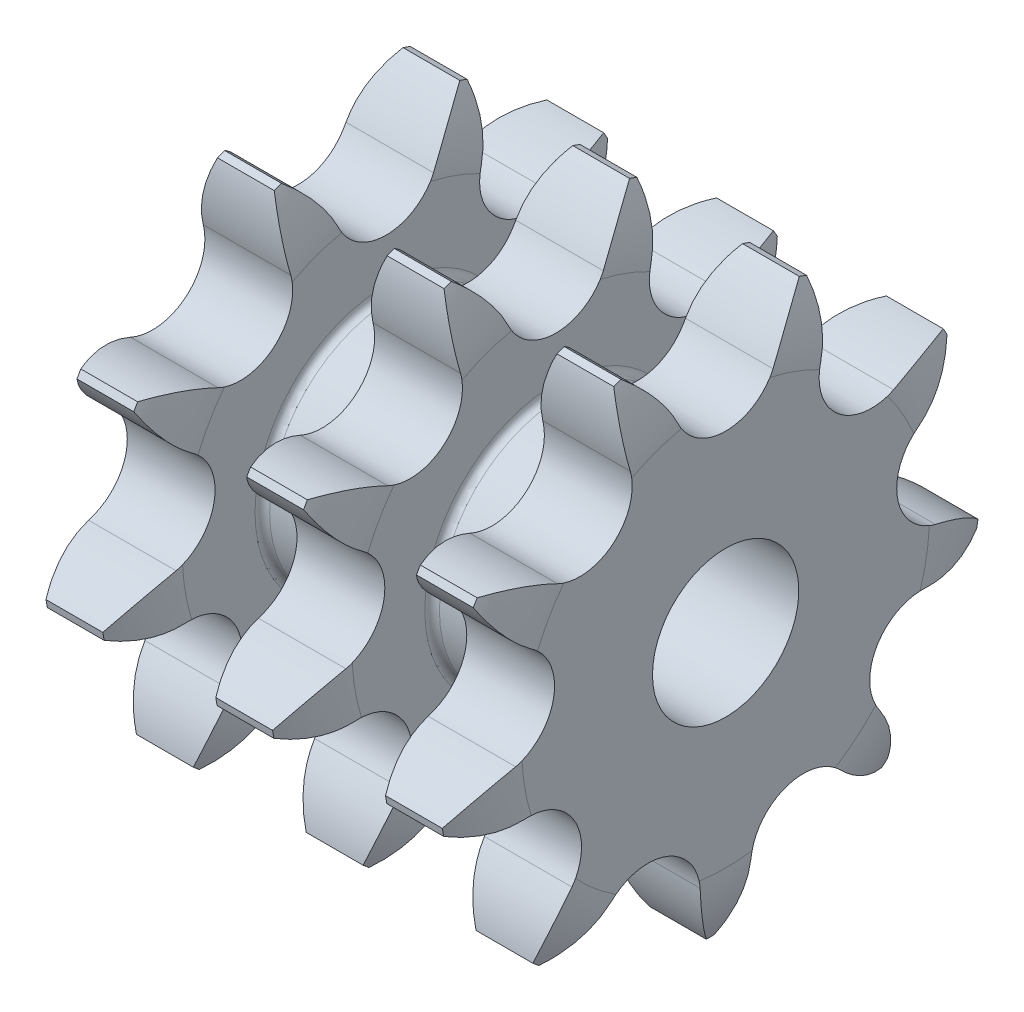
SolidWorks part; units mm, degrees
ref_plane "Plane1" through (0, 0, 0) normal (0, 0, 1) x (1, 0, 0)
ref_plane "Plane2" through (0, 0, 0) normal (0, 1, 0) x (1, 0, 0)
ref_plane "Plane3" through (0, 0, 0) normal (1, 0, 0) x (0, 0, -1)
sketch "Clipboard" plane through (0, 0, 0) normal (0, 1, 0) x (1, 0, 0)
  line L0 (0, 0) -> (12.5436, -1.9867)
  line L1 (-15, 0) -> (100, 0) construction
  line L2 (0, 0) -> (-0.8416, 0.9512)
  line L3 (0, 0) -> (-11.863, 4.5341)
  line L4 (0, 0) -> (3.0618, 0.4849)
  line L5 (0, 0) -> (-2.8109, -1.0484)
  line L6 (0, 0) -> (-29.0469, -19.598)
  line L7 (-0.8416, 0.9512) -> (35.5852, 8.6939)
  line L8 (-76.2, 38.1) -> (-75.2, 38.1)
  line L9 (-73.4259, 41.6592) -> (-72.8306, 41.7344)
  line L10 (-73.4741, 12.7512) -> (-59.5541, 12.7512)
  circle A0 centre (0, 0) radius 4.255
  circle A1 centre (0, 0) radius 10.1515
  circle A2 centre (0, 0) radius 25
  dimension "Num_teeth" = 9
  dimension "Thickness" = 35.04
  dimension "Fillet_rad" = 0.6
sketch "BasProSke" plane through (0, 0, 0) normal (0, 1, 0) x (1, 0, 0)
  line L0 (-10, 0) -> (60, 0) construction
  line L1 (0, 0) -> (0, 16.7129)
  line L2 (0, 0) -> (35.04, 0)
  line L3 (35.04, 0) -> (35.04, 16.7129)
  line L4 (33.77, 22.2487) -> (1.27, 22.2487)
  arc A0 (0, 16.7129) -> (1.27, 22.2487) centre (12.7, 16.7129) cw
  arc A1 (35.04, 16.7129) -> (33.77, 22.2487) centre (22.34, 16.7129) ccw
  dimension "D1" = 12.7
  dimension "Thickness" = 35.04
  dimension "Diameter" = 44.4973
  dimension "G1" = 1.27
revolve "Base-Revolve" add sketch "BasProSke" angle 360 about L0
sketch "GrvSke" plane through (0, 0, 0) normal (0, 1, 0) x (1, 0, 0)
  line L0 (7.2, 16.7129) -> (7.2, 10.7515)
  line L1 (7.8, 10.1515) -> (13.32, 10.1515)
  line L2 (13.92, 10.7515) -> (13.92, 16.7129)
  line L3 (5.93, 22.2487) -> (15.19, 22.2487)
  line L4 (10.56, 0) -> (10.56, 52.07) construction
  line L5 (-10, 0) -> (60, 0) construction
  line L6 (0, 0) -> (35.56, 0) construction
  arc A0 (13.92, 16.7129) -> (15.19, 22.2487) centre (26.62, 16.7129) cw
  arc A1 (7.2, 16.7129) -> (5.93, 22.2487) centre (-5.5, 16.7129) ccw
  arc A2 (7.2, 10.7515) -> (7.8, 10.1515) centre (7.8, 10.7515) ccw
  arc A3 (13.32, 10.1515) -> (13.92, 10.7515) centre (13.32, 10.7515) ccw
  dimension "D1" = 12.7
  dimension "Diameter" = 44.4973
  dimension "Fillet_rad" = 0.6
  dimension "G1" = 1.27
  dimension "Grv_width" = 6.72
revolve "Groove" cut sketch "GrvSke" angle 360 about L6
pattern_linear "Grooves" count 2 spacing 13.92 along (1, 0, 0) of "Groove"
sketch "TooCutSke" plane through (0, 0, 0) normal (1, 0, 0) x (0, 0, -1)
  line L0 (0, 18.6087) -> (3.8949, 16.7925) construction
  line L1 (0, 0) -> (0, 107) construction
  line L2 (0, 18.6087) -> (-10, 18.6087) construction
  line L3 (0, 18.6087) -> (-3.8949, 16.7925) construction
  arc A0 (3.8949, 16.7925) -> (7.8075, 21.3669) centre (14.0756, 12.0451) cw
  arc A1 (3.8949, 16.7925) -> (-3.8949, 16.7925) centre (0, 18.6087) cw
  arc A2 (-3.8949, 16.7925) -> (-7.8075, 21.3669) centre (-14.0756, 12.0451) ccw
  arc A3 (7.8075, 21.3669) -> (-7.8075, 21.3669) centre (0, 0) ccw
extrude "ToothCut" cut sketch "TooCutSke" along normal through all
pattern_circular "TeethCuts" count 9 every 40 about axis through (-10, 0, 0) along (1, 0, 0) of "ToothCut"
sketch "HubNeaOneSke" plane through (0, 0, 0) normal (-1, 0, 0) x (0, 0, 1)
  circle A0 centre (0, 0) radius 10.1515
  dimension "Diameter" = 20.303
extrude "HubNearOne" [suppressed] add sketch "HubNeaOneSke" along normal blind 2.2005
fillet "HubNearOneFillet" [suppressed] radius 0.6
sketch "HubNeaBotSke" plane through (0, 0, 0) normal (-1, 0, 0) x (0, 0, 1)
  circle A0 centre (0, 0) radius 10.1515
  dimension "Diameter" = 20.303
extrude "HubNearBoth" [suppressed] add sketch "HubNeaBotSke" along normal blind 1.1003
fillet "HubNearBothFillet" [suppressed] radius 0.6
ref_plane "FarPln" through (35.04, 0, 0) normal (1, 0, 0) x (0, 0, -1)
sketch "HubFarSke" plane through (35.04, 0, 0) normal (1, 0, 0) x (0, 0, -1)
  circle A0 centre (0, 0) radius 10.1515
  dimension "Diameter" = 20.303
extrude "HubFar" [suppressed] add sketch "HubFarSke" along normal blind 1.1003
fillet "HubFarFillet" [suppressed] radius 0.6
sketch "BorSke" plane through (0, 0, 0) normal (1, 0, 0) x (0, 0, -1)
  circle A0 centre (0, 0) radius 6
  dimension "Diameter" = 12
extrude "Bore" cut sketch "BorSke" along normal mid plane 74.481
sketch "KeySke" plane through (0, 0, 0) normal (1, 0, 0) x (0, 0, -1)
  line L0 (-1, 0) -> (-1, 7)
  line L1 (-1, 7) -> (1, 7)
  line L2 (1, 7) -> (1, 0)
  line L3 (0, 0) -> (0, 34) construction
  line L4 (-1, 0) -> (1, 0)
  dimension "Offset" = 7
  dimension "Width" = 2
extrude "Keyway" [suppressed] cut sketch "KeySke" along normal mid plane 74.481
pattern_circular "Keyway2" [suppressed] count 2 every 90 about axis through (-10, 0, 0) along (1, 0, 0) reverse direction yes
equation "' \"Pitch@Clipboard\" = 12.7"
equation "' \"Num_strands@Clipboard\" = 3"
equation "' \"Num_teeth@Clipboard\" = 9"
equation "' \"Hub_dia@Clipboard\" = 50"
equation "' \"Overall_len@Clipboard\" = 3"
equation "' \"Diameter@BorSke\" = 12"
equation "' \"T_dim@Clipboard\" = 1"
equation "' \"Width@KeySke\" = 2"
equation "' \"Dr@Clipboard\" = 8.51"
equation "' \"Face_width@Clipboard\" = 7.2"
equation "' \"Side_radius@Clipboard\" = 12.7"
equation "' \"Side_relief@Clipboard\" = 1.27"
equation "' \"Transv_pitch@Clipboard\" = 13.92"
equation "' \"Show_teeth@Clipboard\" = 9"
equation "' \"Fillet_rad@Clipboard\" = 0.6"
equation "' \"Plate_wid@Clipboard\" = 11.8"
equation "\"Num_teeth@Clipboard\" = int( \"Num_teeth@Clipboard\" )"
equation "\"Num_teeth@Clipboard\" = ((sgn( \"Num_teeth@Clipboard\" - 5.0)+1)*( \"Num_teeth@Clipboard\" - 5.0))/2 +5.0"
equation "\"Num_teeth@Clipboard\" = ((sgn( \"Num_teeth@Clipboard\" - 200.0)-1)*( \"Num_teeth@Clipboard\" - 200.0))/-2 +200.0"
equation "\"MHD@Clipboard\" = \"Pitch@Clipboard\" * (1.0 / tan(3.14159265 / \"Num_teeth@Clipboard\" )) - 1.05 * \"Plate_wid@Clipboard\" - 2.0 * \"Fillet_rad@Clipboard\" - 1.0"
equation "\"Thickness@Clipboard\"  = \"Face_width@Clipboard\" + (\"Num_strands@Clipboard\" - 1) * \"Transv_pitch@Clipboard\""
equation "\"OAL@Clipboard\" = \"Thickness@Clipboard\" + 2 * \"Fillet_rad@Clipboard\" + 1"
equation "\"MHD@Clipboard\" = ((sgn( \"MHD@Clipboard\" - \"Hub_dia@Clipboard\" )-1)*( \"MHD@Clipboard\" - \"Hub_dia@Clipboard\" ))/-2+ \"Hub_dia@Clipboard\""
equation "\"OAL@Clipboard\" = ((sgn( \"OAL@Clipboard\" - \"Overall_len@Clipboard\" )+1)*( \"OAL@Clipboard\" - \"Overall_len@Clipboard\" ))/2 + \"Overall_len@Clipboard\" + 0.0005"
equation "\"Num_teeth@TeethCuts\" = int( \"Show_teeth@Clipboard\" ) + 1"
equation "\"Num_teeth@TeethCuts\" = ((sgn( \"Num_teeth@TeethCuts\" - \"Num_teeth@Clipboard\" )-1)*( \"Num_teeth@TeethCuts\" - \"Num_teeth@Clipboard\" ))/-2+ \"Num_teeth@Clipboard\""
equation "\"Num_teeth@TeethCuts\" = ((sgn( \"Num_teeth@TeethCuts\" - 2.0)+1)*( \"Num_teeth@TeethCuts\" - 2.0))/2 +2.0"
equation "\"Angle@TeethCuts\" = 360.0 / \"Num_teeth@Clipboard\""
equation "\"Seat_radius@TooCutSke\" = ( \"Pitch@Clipboard\" / 2.0) / sin(3.14159265 / \"Num_teeth@Clipboard\" ) - \"Dr@Clipboard\" / 2.0 + \"Dr@Clipboard\" * 0.505"
equation "\"R1@TooCutSke\"  = \"Dr@Clipboard\" * 0.505"
equation "\"X@TooCutSke\" = 140.0 - (90.0 / \"Num_teeth@Clipboard\")"
equation "\"R2@TooCutSke\" = 0.12 * \"Dr@Clipboard\" * ( \"Num_teeth@Clipboard\" + 2.0)"
equation "\"Overcut@TooCutSke\" = 0.5 + 0.625 * \"Pitch@Clipboard\" - 0.5 * \"Dr@Clipboard\"  +  \"Pitch@Clipboard\" / 2.0 / sin(3.14159265 / \"Num_teeth@Clipboard\" )"
equation "\"Diameter@BasProSke\" = 2.0 * ( 0.625 * \"Pitch@Clipboard\" - 0.5 * \"Dr@Clipboard\"  +  \"Pitch@Clipboard\" / 2.0 / sin(3.14159265 / \"Num_teeth@Clipboard\" ))"
equation "\"Thickness@BasProSke\"  = \"Thickness@Clipboard\""
equation "\"G1@BasProSke\" =  \"Side_relief@Clipboard\""
equation "\"G2@BasProSke\" =  \"Side_relief@Clipboard\""
equation "\"D1@BasProSke\" =  \"Side_radius@Clipboard\""
equation "\"Diameter@GrvSke\" = \"Diameter@BasProSke\""
equation "\"G1@GrvSke\" = \"Side_relief@Clipboard\""
equation "\"D1@GrvSke\" = \"Side_radius@Clipboard\""
equation "\"Grv_diam@GrvSke\" =  \"Pitch@Clipboard\" * (1.0 / tan(3.14159265 / \"Num_teeth@Clipboard\" ))- 1.05 * \"Plate_wid@Clipboard\" - 2.0 * \"Fillet_rad@Clipboard\" - 1.0"
equation "\"Grv_width@GrvSke\" =  \"Transv_pitch@Clipboard\" - \"Face_width@Clipboard\""
equation "\"Offset@GrvSke\" = \"Grv_width@GrvSke\" / 2.0 + \"Face_width@Clipboard\""
equation "\"Fillet_rad@GrvSke\" = \"Fillet_rad@Clipboard\""
equation "\"Offset@Grooves\" = \"Transv_pitch@Clipboard\""
equation "\"Num_grvs@Grooves\" = \"Num_strands@Clipboard\""
equation "\"Num_grvs@Grooves\" = \"Num_grvs@Grooves\" - 1 * sgn( \"Num_grvs@Grooves\" -1)"
equation "\"Diameter@HubNeaOneSke\" = \"MHD@Clipboard\""
equation "\"Length@HubNearOne\" = \"OAL@Clipboard\" - \"Thickness@BasProSke\""
equation "\"Diameter@HubNeaBotSke\" = \"MHD@Clipboard\""
equation "\"Length@HubNearBoth\" = ( \"OAL@Clipboard\" - \"Thickness@BasProSke\" ) / 2.0"
equation "\"D1@HubNearOneFillet\" = \"Fillet_rad@Clipboard\""
equation "\"D1@HubNearBothFillet\" = \"Fillet_rad@Clipboard\""
equation "\"Thickness@FarPln\" = \"Thickness@BasProSke\""
equation "\"Diameter@HubFarSke\" = \"MHD@Clipboard\""
equation "\"Length@HubFar\" = ( \"OAL@Clipboard\" - \"Thickness@BasProSke\" ) / 2.0"
equation "\"D1@HubFarFillet\" = \"Fillet_rad@Clipboard\""
equation "\"D1@Bore\" = \"OAL@Clipboard\" * 2.0"
equation "\"D1@Keyway\" = \"OAL@Clipboard\" * 2.0"
equation "\"Offset@KeySke\" = \"T_dim@Clipboard\" + \"Diameter@BorSke\" / 2.0"
